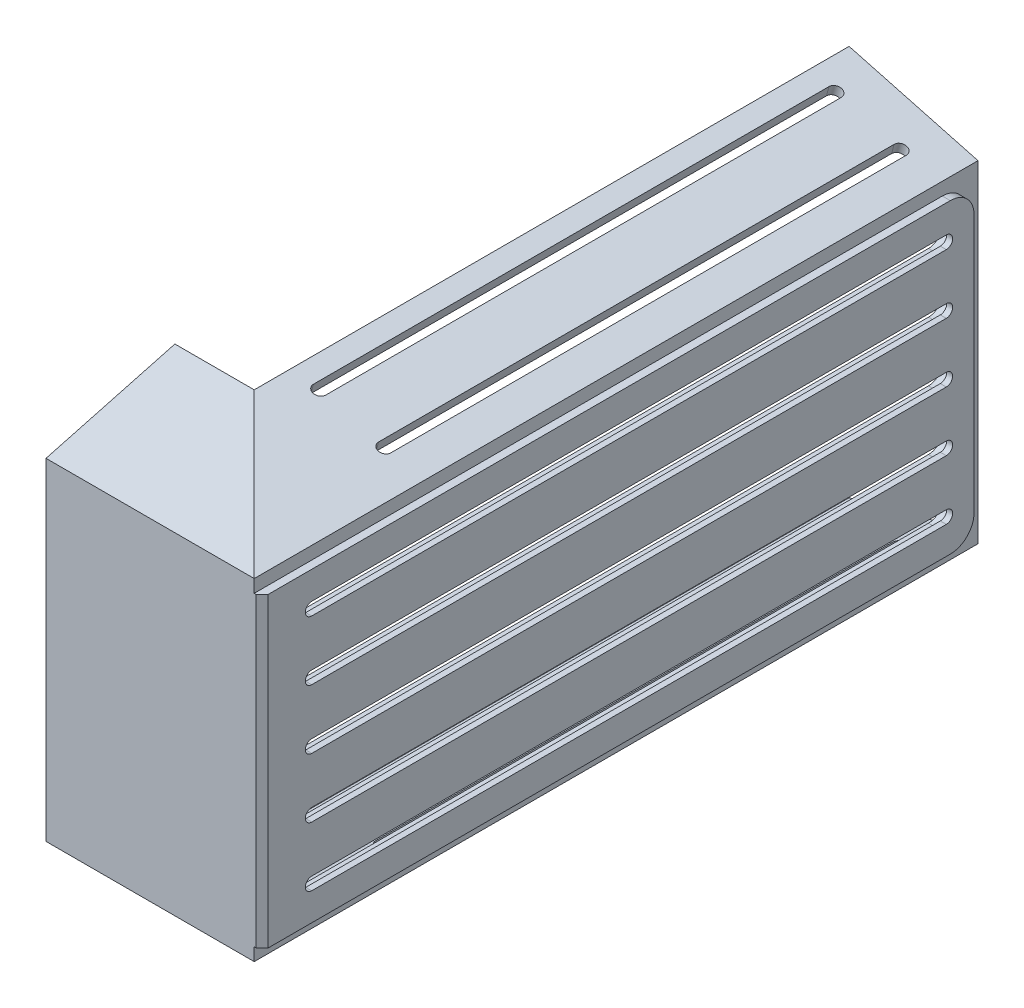
SolidWorks part; units mm, degrees
ref_plane "Front Plane" through (0, 0, 0) normal (0, 0, 1) x (1, 0, 0)
ref_plane "Top Plane" through (0, 0, 0) normal (0, 1, 0) x (1, 0, 0)
ref_plane "Right Plane" through (0, 0, 0) normal (1, 0, 0) x (0, 0, -1)
sketch "Sketch2" plane through (0, 0, 0) normal (0, 1, 0) x (1, 0, 0)
  line L0 (0, 0) -> (50, 0)
  line L1 (50, 0) -> (50, 180)
  dimension "D1" = 50
  dimension "D5" = 180
sketch "Sketch4" plane through (0, 0, 0) normal (1, 0, 0) x (0, 0, -1)
  line L0 (0, -40) -> (0, 40)
  line L1 (0, -40) -> (30, -48.0385)
  line L2 (30, -48.0385) -> (30, -50.5385)
  line L3 (30, -50.5385) -> (-2.5, -41.8301)
  line L4 (-2.5, -41.8301) -> (-2.5, 41.8301)
  line L5 (-2.5, 41.8301) -> (30, 50.5385)
  line L6 (30, 50.5385) -> (30, 48.0385)
  line L7 (30, 48.0385) -> (0, 40)
  line L8 (0, 0) -> (-2.5, 0) construction
  point P2 (0, 0)
  dimension "D1" = 2.5
  dimension "D2" = 80
  dimension "D3" = 30
  dimension "D4" = 105
sweep "Sweep1" add profiles "Sketch4" path "Sketch2"
sketch "Sketch6" plane through (50, 0, 0) normal (-1, 0, 0) x (0, 0, 1)
  line L0 (-10, 30) -> (-170, 30) construction
  line L1 (-10, 28.4) -> (-170, 28.4)
  line L2 (-10, 31.6) -> (-170, 31.6)
  line L3 (-10, 0) -> (-170, 0) construction
  line L4 (0, 0) -> (-180, 0) construction
  line L5 (-10, -1.6) -> (-170, -1.6)
  line L6 (-10, 1.6) -> (-170, 1.6)
  line L7 (-10, -30) -> (-170, -30) construction
  line L8 (-10, -31.6) -> (-170, -31.6)
  line L9 (-10, -28.4) -> (-170, -28.4)
  line L10 (-10, -15) -> (-170, -15) construction
  line L11 (-10, -16.6) -> (-170, -16.6)
  line L12 (-10, -13.4) -> (-170, -13.4)
  line L13 (-10, 15) -> (-170, 15) construction
  line L14 (-10, 13.4) -> (-170, 13.4)
  line L15 (-10, 16.6) -> (-170, 16.6)
  line L16 (-90, 30) -> (-90, 15) construction
  line L17 (-90, 15) -> (-90, 0) construction
  line L18 (-90, 0) -> (-90, -15) construction
  line L19 (-90, -15) -> (-90, -30) construction
  line L20 (0, 40) -> (0, -40) construction
  arc A0 (-10, 28.4) -> (-10, 31.6) centre (-10, 30) ccw
  arc A1 (-170, 31.6) -> (-170, 28.4) centre (-170, 30) ccw
  arc A2 (-10, -1.6) -> (-10, 1.6) centre (-10, 0) ccw
  arc A3 (-170, 1.6) -> (-170, -1.6) centre (-170, 0) ccw
  arc A4 (-10, -31.6) -> (-10, -28.4) centre (-10, -30) ccw
  arc A5 (-170, -28.4) -> (-170, -31.6) centre (-170, -30) ccw
  arc A6 (-10, -16.6) -> (-10, -13.4) centre (-10, -15) ccw
  arc A7 (-170, -13.4) -> (-170, -16.6) centre (-170, -15) ccw
  arc A8 (-10, 13.4) -> (-10, 16.6) centre (-10, 15) ccw
  arc A9 (-170, 16.6) -> (-170, 13.4) centre (-170, 15) ccw
  point P2 (-90, 30)
  point P7 (-90, 0)
  point P16 (-90, -30)
  point P23 (-90, -15)
  point P30 (-90, 15)
  dimension "D1" = 3.2
  dimension "D2" = 15
  dimension "D3" = 160
  dimension "D4" = 10
extrude "Cut-Extrude1" cut sketch "Sketch6" against normal through all
sketch "Sketch7" plane through (52.5, 0, 0) normal (1, 0, 0) x (0, 0, -1)
  line L0 (170, -31.6) -> (10, -31.6) construction
  line L3 (10, -28.4) -> (170, -28.4) construction
  line L4 (170, -16.6) -> (10, -16.6) construction
  line L13 (10, -13.4) -> (170, -13.4) construction
  line L16 (10, 1.6) -> (170, 1.6) construction
  line L19 (170, -1.6) -> (10, -1.6) construction
  line L22 (10, 0) -> (3, 0) construction
  line L23 (3, 38.6) -> (177, 38.6)
  line L24 (3, 38.6) -> (3, -38.6)
  line L25 (3, -38.6) -> (177, -38.6)
  line L26 (177, 38.6) -> (177, -38.6)
  line L27 (170, 0) -> (177, 0) construction
  line L28 (170, 13.4) -> (10, 13.4) construction
  line L29 (10, 16.6) -> (170, 16.6) construction
  line L30 (170, 28.4) -> (10, 28.4) construction
  line L31 (10, 31.6) -> (170, 31.6) construction
  line L32 (170, -31.6) -> (10, -31.6)
  line L33 (10, -28.4) -> (170, -28.4)
  line L34 (170, -16.6) -> (10, -16.6)
  line L35 (10, -13.4) -> (170, -13.4)
  line L36 (10, 1.6) -> (170, 1.6)
  line L37 (170, -1.6) -> (10, -1.6)
  line L38 (170, 13.4) -> (10, 13.4)
  line L39 (10, 16.6) -> (170, 16.6)
  line L40 (170, 28.4) -> (10, 28.4)
  line L41 (10, 31.6) -> (170, 31.6)
  arc A0 (10, -28.4) -> (10, -31.6) centre (10, -30) ccw construction
  arc A1 (170, -31.6) -> (170, -28.4) centre (170, -30) ccw construction
  arc A2 (170, -16.6) -> (170, -13.4) centre (170, -15) ccw construction
  arc A3 (10, -13.4) -> (10, -16.6) centre (10, -15) ccw construction
  arc A4 (170, -1.6) -> (170, 1.6) centre (170, 0) ccw construction
  arc A5 (10, 1.6) -> (10, -1.6) centre (10, 0) ccw construction
  arc A6 (10, 16.6) -> (10, 13.4) centre (10, 15) ccw construction
  arc A7 (170, 13.4) -> (170, 16.6) centre (170, 15) ccw construction
  arc A8 (170, 28.4) -> (170, 31.6) centre (170, 30) ccw construction
  arc A9 (10, 31.6) -> (10, 28.4) centre (10, 30) ccw construction
  arc A10 (10, -28.4) -> (10, -31.6) centre (10, -30) ccw
  arc A11 (170, -31.6) -> (170, -28.4) centre (170, -30) ccw
  arc A12 (170, -16.6) -> (170, -13.4) centre (170, -15) ccw
  arc A13 (10, -13.4) -> (10, -16.6) centre (10, -15) ccw
  arc A14 (170, -1.6) -> (170, 1.6) centre (170, 0) ccw
  arc A15 (10, 1.6) -> (10, -1.6) centre (10, 0) ccw
  arc A16 (10, 16.6) -> (10, 13.4) centre (10, 15) ccw
  arc A17 (170, 13.4) -> (170, 16.6) centre (170, 15) ccw
  arc A18 (170, 28.4) -> (170, 31.6) centre (170, 30) ccw
  arc A19 (10, 31.6) -> (10, 28.4) centre (10, 30) ccw
  dimension "D1" = 7
  dimension "D2" = 8.6
extrude "Boss-Extrude1" add sketch "Sketch7" along normal blind 2
sketch "Sketch9" plane through (50, 0, 0) normal (-1, 0, 0) x (0, 0, 1)
  line L0 (-170, 30) -> (-10, 30) construction
  line L1 (-170, 33.6) -> (-10, 33.6)
  line L2 (-170, 26.4) -> (-10, 26.4)
  line L3 (-170, 15) -> (-10, 15) construction
  line L4 (-170, 18.6) -> (-10, 18.6)
  line L5 (-170, 11.4) -> (-10, 11.4)
  line L6 (-170, 0) -> (-10, 0) construction
  line L7 (-170, 3.6) -> (-10, 3.6)
  line L8 (-170, -3.6) -> (-10, -3.6)
  line L9 (-170, -15) -> (-10, -15) construction
  line L10 (-170, -11.4) -> (-10, -11.4)
  line L11 (-170, -18.6) -> (-10, -18.6)
  line L12 (-170, -30) -> (-10, -30) construction
  line L13 (-170, -26.4) -> (-10, -26.4)
  line L14 (-170, -33.6) -> (-10, -33.6)
  line L15 (-10, 31.6) -> (-170, 31.6) construction
  arc A0 (-170, 33.6) -> (-170, 26.4) centre (-170, 30) ccw
  arc A1 (-10, 26.4) -> (-10, 33.6) centre (-10, 30) ccw
  arc A2 (-170, 18.6) -> (-170, 11.4) centre (-170, 15) ccw
  arc A3 (-10, 11.4) -> (-10, 18.6) centre (-10, 15) ccw
  arc A4 (-170, 3.6) -> (-170, -3.6) centre (-170, 0) ccw
  arc A5 (-10, -3.6) -> (-10, 3.6) centre (-10, 0) ccw
  arc A6 (-170, -11.4) -> (-170, -18.6) centre (-170, -15) ccw
  arc A7 (-10, -18.6) -> (-10, -11.4) centre (-10, -15) ccw
  arc A8 (-170, -26.4) -> (-170, -33.6) centre (-170, -30) ccw
  arc A9 (-10, -33.6) -> (-10, -26.4) centre (-10, -30) ccw
  point P4 (-90, 30)
  point P9 (-90, 15)
  point P18 (-90, 0)
  point P27 (-90, -15)
  point P36 (-90, -30)
  dimension "D1" = 2
extrude "Cut-Extrude2" cut sketch "Sketch9" against normal blind 3
fillet "Fillet1" radius 6 2 edges at (53.5, 38.6, -177) (53.5, -38.6, -177)
chamfer "Chamfer1" distance 6 angle 45 1 edges at (52.5, 0, -3)
sketch "Sketch10" plane through (13.9744, 52.153, 0) normal (0.2588, 0.9659, 0) x (0.9659, -0.2588, 0)
  line L0 (12.9382, 170) -> (12.9382, 40) construction
  line L1 (14.5382, 170) -> (14.5382, 40)
  line L2 (11.3382, 170) -> (11.3382, 40)
  line L3 (29.9382, 170) -> (29.9382, 40) construction
  line L4 (31.5382, 170) -> (31.5382, 40)
  line L5 (28.3382, 170) -> (28.3382, 40)
  line L7 (6.2382, 30) -> (6.2382, 180) construction
  line L9 (45.2925, 170) -> (43.8436, 170) construction
  line L12 (-13.0803, 30) -> (6.2382, 30) construction
  arc A0 (14.5382, 170) -> (11.3382, 170) centre (12.9382, 170) ccw
  arc A1 (11.3382, 40) -> (14.5382, 40) centre (12.9382, 40) ccw
  arc A2 (31.5382, 170) -> (28.3382, 170) centre (29.9382, 170) ccw
  arc A3 (28.3382, 40) -> (31.5382, 40) centre (29.9382, 40) ccw
  point P2 (12.9382, 105)
  point P7 (29.9382, 105)
  dimension "D1" = 5.1
  dimension "D2" = 17
  dimension "D3" = 3.2
  dimension "D4" = 10
extrude "Cut-Extrude3" cut sketch "Sketch10" against normal up to next
mirror "Mirror1" about plane through (0, 0, 0) normal (0, 1, 0) of "Cut-Extrude3"
equation "\"3..00mm\"=4"
